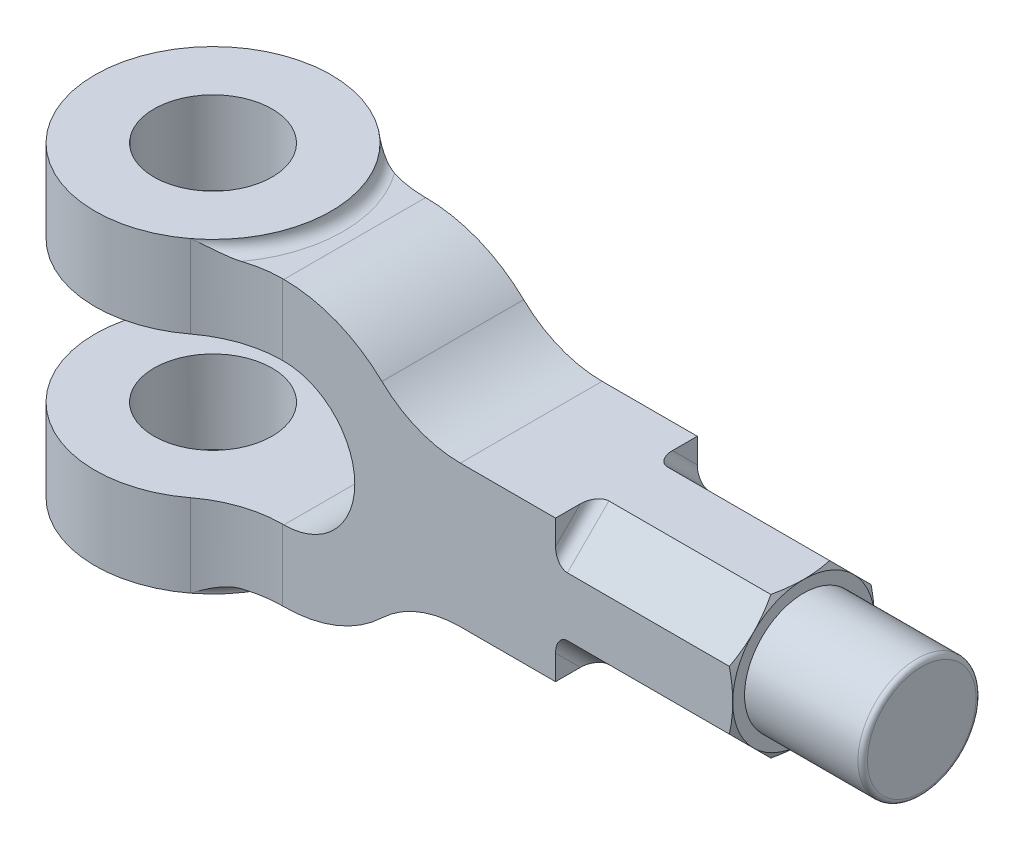
SolidWorks part; units mm, degrees
ref_plane "Front Plane" through (0, 0, 0) normal (0, 0, 1) x (1, 0, 0)
ref_plane "Top Plane" through (0, 0, 0) normal (0, 1, 0) x (1, 0, 0)
ref_plane "Right Plane" through (0, 0, 0) normal (1, 0, 0) x (0, 0, -1)
sketch "Sketch2" plane through (0, 0, 0) normal (0, 0, 1) x (1, 0, 0)
  line L0 (0, 0) -> (29333.7056, 0) construction
  line L1 (0, 30) -> (-30, 30)
  line L2 (-30, 30) -> (-30, 15)
  line L3 (-30, 15) -> (0, 15)
  line L4 (-30, -15) -> (0, -15)
  line L5 (-30, -30) -> (-30, -15)
  line L6 (0, -30) -> (-30, -30)
  line L8 (95, -15) -> (37.3497, -15)
  line L9 (95, -15) -> (95, 15)
  line L10 (95, 15) -> (37.3497, 15)
  arc A0 (0, 30) -> (20.7498, 21.6667) centre (0, 0) cw
  arc A1 (0, 15) -> (0, -15) centre (0, 0) cw
  arc A2 (20.7498, -21.6667) -> (0, -30) centre (0, 0) cw
  arc A3 (37.3497, -15) -> (20.7498, -21.6667) centre (37.3497, -39) ccw
  arc A4 (37.3497, 15) -> (20.7498, 21.6667) centre (37.3497, 39) cw
  point P17 (25.9808, -15)
  dimension "D1" = 30
  dimension "D2" = 15
  dimension "D6" = 24
  dimension "D3" = 30
  dimension "D4" = 30
  dimension "D5" = 95
extrude "Boss-Extrude2" add sketch "Sketch2" along normal mid plane 30
sketch "Sketch3" plane through (0, 30, 0) normal (0, 1, 0) x (1, 0, 0)
  line L0 (-30, -15) -> (-30, 15) construction
  circle A0 centre (-30, 0) radius 25
  dimension "D1" = 50
extrude "Boss-Extrude3" add sketch "Sketch3" against normal blind 15 and the other way blind 2.5
mirror "Mirror1" about plane through (0, 0, 0) normal (0, 1, 0) of "Boss-Extrude3"
hole_wizard "Ø25.0mm Dowel Hole1" positions "Sketch4" profile "Sketch5" hole size "Ø25.0" standard "ISO" end condition through all
sketch "Sketch4" plane through (0, 32.5, 0) normal (0, 1, 0) x (1, 0, 0)
  point P0 (-30, 0)
sketch "Sketch5" plane through (-30, 32.5, 0) normal (1, 0, 0) x (0, 0, 1)
  line L0 (0, 0) -> (0, 65)
  line L1 (0, 65) -> (12.5, 65)
  line L2 (12.5, 65) -> (12.5, 0)
  line L5 (12.5, 0) -> (0, 0)
  line L11 (0, -6.35) -> (0, 107.95) construction
  dimension "Thru Hole Dia." = 25
  dimension "Thru Hole Depth" = 65
fillet "Fillet1" radius 24 4 edges at (-10, -22.5, -15) (-10, 22.5, -15) (-10, -22.5, 15) (-10, 22.5, 15)
fillet "Fillet2" radius 2.5 2 edges at (-5, -30, 0) (-5, 30, 0)
sketch "Sketch6" plane through (95, 0, 0) normal (1, 0, 0) x (0, 0, -1)
  line L0 (-15, 15) -> (15, 15) construction
  line L1 (15, 6.2132) -> (6.2132, 15)
  line L2 (6.2132, 15) -> (-6.2132, 15)
  line L3 (-6.2132, 15) -> (-15, 6.2132)
  line L4 (-15, 6.2132) -> (-15, -6.2132)
  line L5 (-15, -6.2132) -> (-6.2132, -15)
  line L6 (-6.2132, -15) -> (6.2132, -15)
  line L7 (6.2132, -15) -> (15, -6.2132)
  line L8 (15, -6.2132) -> (15, 6.2132)
  circle A0 centre (0, 0) radius 15 construction
extrude "Cut-Extrude2" cut sketch "Sketch6" against normal blind 37.5 and the other way through all flip side to cut
fillet "Fillet3" radius 2.5 4 edges at (57.5, 10.6066, -10.6066) (57.5, -10.6066, -10.6066) (57.5, -10.6066, 10.6066) (57.5, 10.6066, 10.6066)
sketch "Sketch7" plane through (95, 0, 0) normal (1, 0, 0) x (0, 0, -1)
  circle A0 centre (0, 0) radius 12.5
  dimension "D1" = 25
extrude "Boss-Extrude4" add sketch "Sketch7" along normal blind 25
sketch "Sketch8" plane through (0, 0, 0) normal (0, 0, 1) x (1, 0, 0)
  line L0 (0, 0) -> (50000, 0) construction
  line L1 (95, 15) -> (95, 41.592)
  line L2 (95, 41.592) -> (79.6471, 41.592)
  line L3 (79.6471, 41.592) -> (95, 15)
  dimension "D1" = 30
revolve "Cut-Revolve1" cut sketch "Sketch8" angle 360 about L0
fillet "Fillet4" radius 1 1 edges at (120, 0, -12.5)
